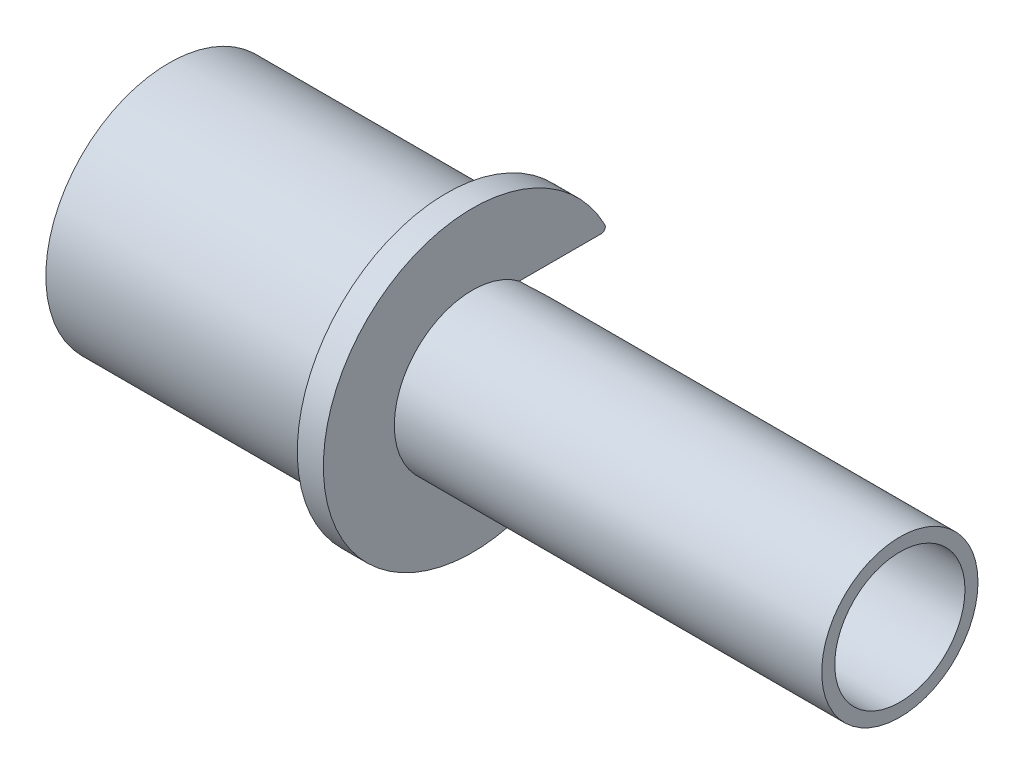
SolidWorks part; units mm, degrees
material "6061-T6 (SS)"
ref_plane "Front Plane" through (0, 0, 0) normal (0, 0, 1) x (1, 0, 0)
ref_plane "Top Plane" through (0, 0, 0) normal (0, 1, 0) x (1, 0, 0)
ref_plane "Right Plane" through (0, 0, 0) normal (1, 0, 0) x (0, 0, -1)
sketch "Sketch1" plane through (0, 0, 0) normal (0, 0, 1) x (1, 0, 0)
  line L0 (0, 0) -> (-16.6687, 0) construction
  line L1 (2.2375, 3.9687) -> (2.2375, 4.7625)
  line L2 (2.2375, 4.7625) -> (-23.8125, 4.7625)
  line L3 (-23.8125, 4.7625) -> (-23.8125, 9.0875)
  line L4 (-23.8125, 9.0875) -> (-25.4, 9.0875)
  line L5 (-25.4, 9.0875) -> (-25.4, 7.5)
  line L6 (-25.4, 7.5) -> (-42.315, 7.5)
  line L7 (-42.315, 7.5) -> (-42.315, 3.9687)
  line L8 (-42.315, 3.9687) -> (2.2375, 3.9687)
  line L9 (-25.4, -15.27) -> (-25.4, 15.27) construction
  line L10 (-50.8, -5.5562) -> (-50.8, 5.5563) construction
  line L14 (2.2375, -11.375) -> (2.2375, 11.375) construction
  dimension "D1" = 7.9375
  dimension "D4" = 15
  dimension "D3" = 9.525
  dimension "D2" = 1.5875
  dimension "D5" = 1.5875
  dimension "D6" = 8.485
revolve "Revolve1" add sketch "Sketch1" angle 360 about L0
sketch "Sketch2" plane through (2.2375, 0, 0) normal (1, 0, 0) x (0, 0, -1)
  line L0 (1.3441, 3.7342) -> (8.2848, 3.7342)
  line L1 (8.2848, -3.7342) -> (1.3441, -3.7342)
  line L2 (0, 0) -> (14.3216, 0) construction
  circle A0 centre (0, 0) radius 3.9687 construction
  circle A1 centre (0, 0) radius 9.0875 construction
  arc A2 (1.3441, 3.7342) -> (1.3441, -3.7342) centre (0, 0) cw
  arc A3 (8.2848, 3.7342) -> (8.2848, -3.7342) centre (0, 0) cw
  arc A4 (3.6742, 3.7342) -> (3.6742, -3.7342) centre (0, 0) cw construction
  circle A5 centre (5.2387, 0) radius 1.27 construction
  circle A6 centre (4.623, 2.4642) radius 1.27 construction
  circle A7 centre (4.623, -2.4642) radius 1.27 construction
  dimension "D1" = 1.27
  dimension "D2" = 2.54
extrude "Cut-Extrude1" [suppressed] cut sketch "Sketch2" against normal through all both
sketch "Sketch3" plane through (0, 0, 0) normal (0, 0, 1) x (1, 0, 0)
  line L0 (-42.315, 3.81) -> (-42.315, -3.81)
  line L1 (-42.315, 7.5) -> (-42.315, -7.5) construction
  line L2 (-42.315, -3.81) -> (-23.8125, -3.81)
  line L4 (-23.8125, 3.81) -> (-42.315, 3.81)
  line L5 (-20.6375, -0.635) -> (-20.6375, 0.635)
  line L6 (-20.6375, 0) -> (0, 0) construction
  line L8 (-23.8125, -9.0875) -> (-23.8125, 9.0875) construction
  arc A1 (-23.8125, -3.81) -> (-20.6375, -0.635) centre (-23.8125, -0.635) ccw
  arc A2 (-20.6375, 0.635) -> (-23.8125, 3.81) centre (-23.8125, 0.635) ccw
  dimension "D1" = 7.62
  dimension "D2" = 3.175
extrude "Cut-Extrude2" cut sketch "Sketch3" against normal up to next
fillet "Fillet1" radius 0.254 4 edges at (-24.6062, 3.81, -8.2502) (-24.6062, -3.81, -8.2502) (-33.8575, -3.81, -6.4602) (-33.8575, 3.81, -6.4602)
equation "\"bearing1\"=0.273438"
equation "\"D1@Sketch1\"=5/16"
equation "\"D4@Sketch1\"=15mm"
equation "\"D6@Sketch1\"=.275+1.5mm"
